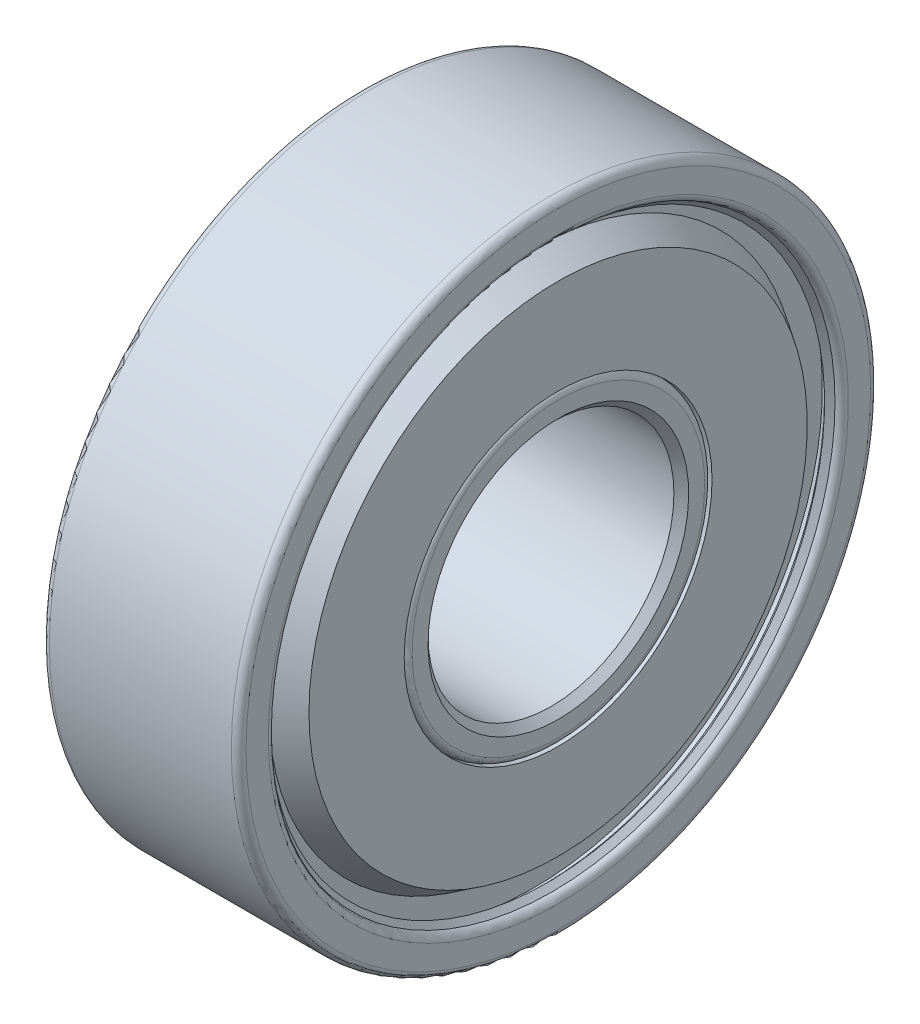
SolidWorks part; units mm, degrees
ref_plane "Frontale" through (0, 0, 0) normal (0, 0, 1) x (1, 0, 0)
ref_plane "Superiore" through (0, 0, 0) normal (0, 1, 0) x (1, 0, 0)
ref_plane "Destro" through (0, 0, 0) normal (1, 0, 0) x (0, 0, -1)
sketch "Schizzo1" plane through (0, 0, 0) normal (0, 0, 1) x (1, 0, 0)
  line L0 (-4, 0) -> (4, 0) construction
  line L1 (0, 13) -> (0, -13) construction
  line L10 (-4, 13) -> (-4, -13)
  line L11 (4, -13) -> (-4, -13)
  line L12 (4, 13) -> (-4, 13)
  line L13 (4, 13) -> (4, -13)
  line L14 (-4, 5) -> (4, 5)
  line L15 (-4, -5) -> (4, -5)
  line L16 (-4, 6.25) -> (-2.75, 6.25)
  line L17 (-2.75, 6.25) -> (-2.75, 7.5)
  line L18 (4, 6.25) -> (2.75, 6.25)
  line L19 (2.75, 6.25) -> (2.75, 7.5)
  line L20 (-2.75, 7.5) -> (-1.6771, 7.5)
  line L21 (-4, 11.5) -> (-3.75, 11.5)
  line L22 (-3.75, 11.5) -> (-3.2617, 11.9864)
  line L23 (-3.2617, 11.9864) -> (-2.75, 11.9864)
  line L24 (-2.75, 11.9864) -> (-2.75, 10.6364)
  line L25 (4, 11.5) -> (3.75, 11.5)
  line L26 (3.75, 11.5) -> (3.2617, 11.9864)
  line L27 (3.2617, 11.9864) -> (2.75, 11.9864)
  line L28 (2.75, 11.9864) -> (2.75, 10.6364)
  line L29 (-2.75, 10.6364) -> (-1.5442, 10.6364)
  line L30 (1.6771, 7.5) -> (2.75, 7.5)
  line L31 (1.5442, 10.6364) -> (2.75, 10.6364)
  line L32 (-4, -6.25) -> (-2.75, -6.25)
  line L33 (-2.75, -6.25) -> (-2.75, -7.5)
  line L34 (4, -6.25) -> (2.75, -6.25)
  line L35 (2.75, -6.25) -> (2.75, -7.5)
  line L36 (-2.75, -7.5) -> (-1.6771, -7.5)
  line L37 (1.6771, -7.5) -> (2.75, -7.5)
  line L38 (-4, -11.5) -> (-3.75, -11.5)
  line L39 (-3.75, -11.5) -> (-3.2617, -11.9864)
  line L40 (-3.2617, -11.9864) -> (-2.75, -11.9864)
  line L41 (-2.75, -11.9864) -> (-2.75, -10.6364)
  line L42 (4, -11.5) -> (3.75, -11.5)
  line L43 (3.75, -11.5) -> (3.2617, -11.9864)
  line L44 (3.2617, -11.9864) -> (2.75, -11.9864)
  line L45 (2.75, -11.9864) -> (2.75, -10.6364)
  line L46 (-2.75, -10.6364) -> (-1.5442, -10.6364)
  line L47 (1.5442, -10.6364) -> (2.75, -10.6364)
  circle A1 centre (0, 9) radius 2.25
  circle A2 centre (0, -9) radius 2.25
  dimension "D4" = 4.5
  dimension "D1" = 10
  dimension "D2" = 8
  dimension "D3" = 26
  dimension "D5" = 18
sketch "Schizzo2" plane through (0, 0, 0) normal (0, 0, 1) x (1, 0, 0)
  line L0 (4, 13) -> (-4, 13) construction
  line L1 (4, 13) -> (-4, 13)
  line L2 (-4, 13) -> (-4, -13) construction
  line L3 (-4, 11.5) -> (-3.75, 11.5) construction
  line L4 (-3.75, 11.5) -> (-3.2617, 11.9864) construction
  line L5 (-3.2617, 11.9864) -> (-2.75, 11.9864) construction
  line L6 (-2.75, 11.9864) -> (-2.75, 10.6364) construction
  line L7 (-2.75, 10.6364) -> (-1.5442, 10.6364) construction
  line L8 (1.5442, 10.6364) -> (2.75, 10.6364) construction
  line L9 (2.75, 11.9864) -> (2.75, 10.6364) construction
  line L10 (3.2617, 11.9864) -> (2.75, 11.9864) construction
  line L11 (3.75, 11.5) -> (3.2617, 11.9864) construction
  line L12 (4, 11.5) -> (3.75, 11.5) construction
  line L13 (4, 13) -> (4, -13) construction
  line L14 (-4, 13) -> (-4, 11.5)
  line L15 (-4, 11.5) -> (-3.75, 11.5)
  line L16 (-3.75, 11.5) -> (-3.2617, 11.9864)
  line L17 (-3.2617, 11.9864) -> (-2.75, 11.9864)
  line L18 (-2.75, 11.9864) -> (-2.75, 10.6364)
  line L19 (-2.75, 10.6364) -> (-1.5442, 10.6364)
  line L20 (1.5442, 10.6364) -> (2.75, 10.6364)
  line L21 (2.75, 11.9864) -> (2.75, 10.6364)
  line L22 (3.2617, 11.9864) -> (2.75, 11.9864)
  line L23 (3.75, 11.5) -> (3.2617, 11.9864)
  line L24 (4, 11.5) -> (3.75, 11.5)
  line L25 (4, 13) -> (4, 11.5)
  line L26 (-4, 0) -> (4, 0) construction
  circle A0 centre (0, 9) radius 2.25 construction
  arc A1 (1.5442, 10.6364) -> (-1.5442, 10.6364) centre (0, 9) ccw
revolve "Rivoluzione1" add sketch "Schizzo2" angle 360 about L26
sketch "Schizzo3" plane through (0, 0, 0) normal (0, 0, 1) x (1, 0, 0)
  line L0 (-2.75, 7.5) -> (-1.6771, 7.5) construction
  line L1 (-2.75, 7.5) -> (-1.6771, 7.5)
  line L2 (-2.75, 6.25) -> (-2.75, 7.5) construction
  line L3 (-4, 6.25) -> (-2.75, 6.25) construction
  line L4 (-4, 13) -> (-4, -13) construction
  line L5 (-4, 5) -> (4, 5) construction
  line L6 (1.6771, 7.5) -> (2.75, 7.5) construction
  line L7 (2.75, 6.25) -> (2.75, 7.5) construction
  line L8 (4, 6.25) -> (2.75, 6.25) construction
  line L9 (4, 13) -> (4, -13) construction
  line L10 (-2.75, 6.25) -> (-2.75, 7.5)
  line L11 (-4, 6.25) -> (-2.75, 6.25)
  line L12 (-4, 6.25) -> (-4, 5)
  line L13 (-4, 5) -> (4, 5)
  line L14 (1.6771, 7.5) -> (2.75, 7.5)
  line L15 (2.75, 6.25) -> (2.75, 7.5)
  line L16 (4, 6.25) -> (2.75, 6.25)
  line L17 (4, 6.25) -> (4, 5)
  line L18 (-4, 0) -> (4, 0) construction
  circle A0 centre (0, 9) radius 2.25 construction
  arc A1 (-1.6771, 7.5) -> (1.6771, 7.5) centre (0, 9) ccw
revolve "Rivoluzione2" add sketch "Schizzo3" angle 360 about L18
fillet "Raccordo1" radius 0.3 4 edges at (4, 0, 11.5) (-4, 0, 11.5) (-4, 0, 13) (4, 0, 13)
fillet "Raccordo2" radius 0.3 2 edges at (-4, -6.25, 0) (4, -6.25, 0)
chamfer "Smusso1" distance 0.3 angle 45 2 edges at (4, -5, 0) (-4, -5, 0)
sketch "Schizzo4" plane through (0, 0, 0) normal (0, 0, 1) x (1, 0, 0)
  line L0 (-2.2, 9) -> (2.2, 9) construction
  line L1 (-2.2, 9) -> (2.2, 9)
  arc A0 (2.2, 9) -> (-2.2, 9) centre (0, 9) ccw
  dimension "D1" = 4.4
revolve "Rivoluzione3" add sketch "Schizzo4" angle 360 about L0
ref_axis "Assi1" through (3.75, 0, 0) along (-1, 0, 0)
pattern_circular "RipetizioneCircolare1" count 10 over 360 about axis through (3.75, 0, 0) along (-1, 0, 0) of bodies 103
sketch "Schizzo5" plane through (0, 0, 0) normal (0, 0, 1) x (1, 0, 0)
  line L0 (-3.75, 11.5) -> (-3.5383, 11.2875)
  line L1 (-3.75, 11.5) -> (-3.2617, 11.9864)
  line L2 (-3.2617, 11.9864) -> (-2.75, 11.9864)
  line L3 (-2.75, 11.9864) -> (-2.75, 10.6364)
  line L4 (-2.75, 10.6364) -> (-3.75, 10)
  line L5 (-3.75, 10) -> (-3.75, 6.5)
  line L6 (-3.75, 6.5) -> (-3, 6.5)
  line L8 (-4, 6.25) -> (-2.75, 6.25) construction
  line L9 (-4, 13) -> (-4, -13) construction
  line L10 (-4, 0) -> (4, 0) construction
  dimension "D1" = 0.75
  dimension "D2" = 0.3
  dimension "D3" = 90
  dimension "D4" = 3.5
  dimension "D5" = 0.25
  dimension "D6" = 0.25
revolve "Rivoluzione-Sottile1" add sketch "Schizzo5" angle 360 about L10 wall 0.24
mirror "Specchia1" about plane through (0, 0, 0) normal (1, 0, 0) of bodies 113
